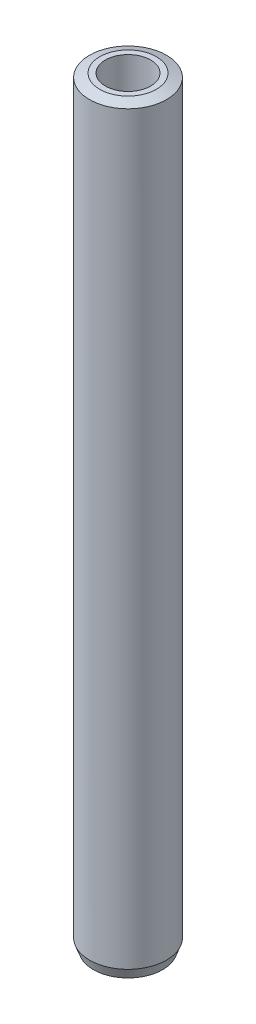
SolidWorks part; units mm, degrees
ref_plane "Front Plane" through (0, 0, 0) normal (0, 0, 1) x (1, 0, 0)
ref_plane "Top Plane" through (0, 0, 0) normal (0, 1, 0) x (1, 0, 0)
ref_plane "Right Plane" through (0, 0, 0) normal (1, 0, 0) x (0, 0, -1)
sketch "Sketch1" plane through (0, 0, 0) normal (0, 1, 0) x (1, 0, 0)
  circle A0 centre (0, 0) radius 22.5
  dimension "SHAFT_OD" = 45
extrude "Boss-Extrude1" add sketch "Sketch1" along normal blind 443.7593
sketch "Sketch2" plane through (0, 0, 0) normal (0, 1, 0) x (1, 0, 0)
  circle A0 centre (0, 0) radius 13.231
  dimension "BORE_D" = 26.462
extrude "Cut-Extrude1" cut sketch "Sketch2" along normal through all
chamfer "Chamfer1" distance 2.2198 angle 69.577 2 edges at (0, 443.7593, 22.5) (0, 0, 22.5) first distance on face at (0, 443.7593, 22.5) first distance on face at (0, 0, 13.231)
